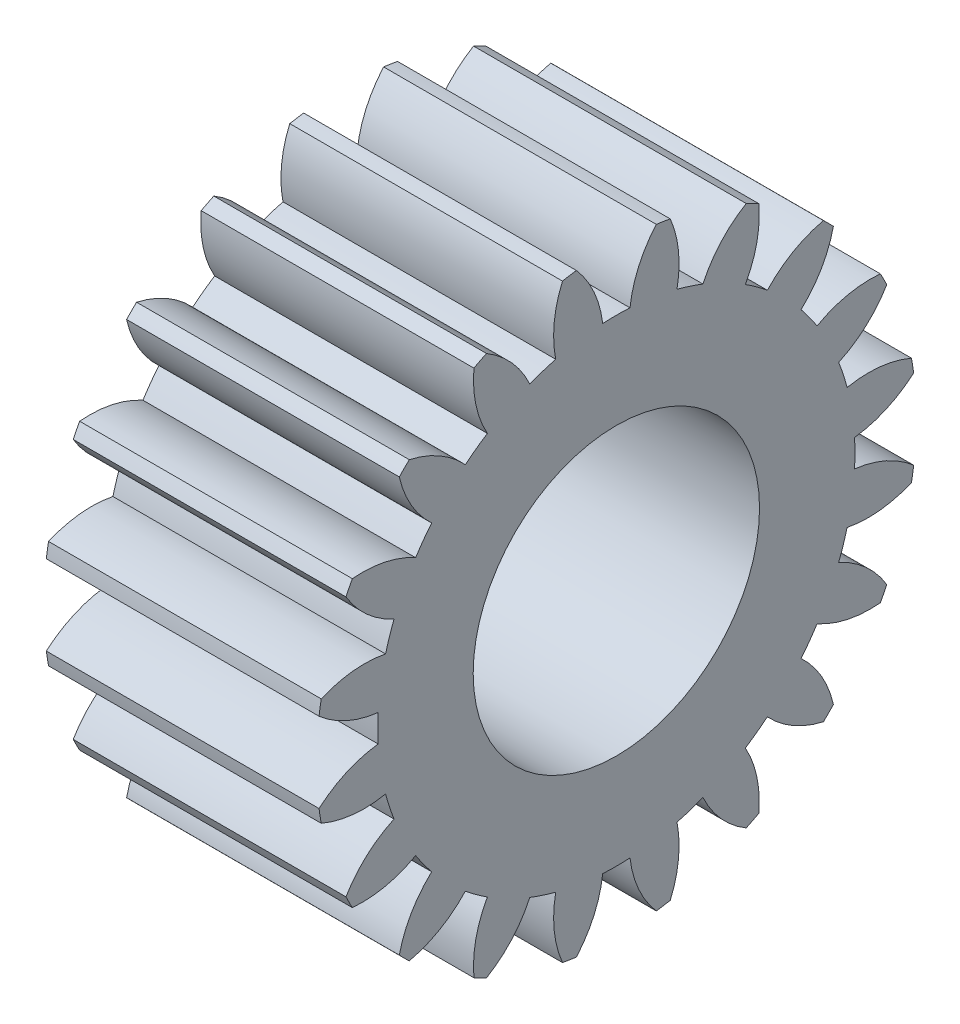
SolidWorks part; units mm, degrees
ref_plane "Plane1" through (0, 0, 0) normal (0, 0, 1) x (1, 0, 0)
ref_plane "Plane2" through (0, 0, 0) normal (0, 1, 0) x (1, 0, 0)
ref_plane "Plane3" through (0, 0, 0) normal (1, 0, 0) x (0, 0, -1)
sketch "HoldingSke" plane through (0, 0, 0) normal (0, 1, 0) x (1, 0, 0)
  line L0 (0, 0) -> (0.9397, -0.342)
  line L1 (-15, 0) -> (100, 0) construction
  line L2 (0, 0) -> (-2.1039, 2.3779)
  line L3 (0, 0) -> (-11.863, 4.5341)
  line L4 (0, 0) -> (8.1152, 2.9537)
  line L5 (0, 0) -> (-46.8476, -17.4728)
  line L6 (0, 0) -> (-8.2896, -5.593)
  line L7 (-2.1039, 2.3779) -> (8.6586, 51.2059)
  line L8 (-76.2, 54.61) -> (-76.1, 54.61)
  line L9 (-71.009, 38.7566) -> (-53.1078, 45.2721)
  line L10 (-76.2, 71.12) -> (104.1128, 71.12)
  line L11 (0, 0) -> (-10, 0)
  line L12 (-76.2, 101.6) -> (-76.162, 101.6)
  line L13 (24.9733, 27.94) -> (52.9518, 28.4284)
  line L14 (24.9733, 27.94) -> (24.9743, 27.94)
  line L15 (24.9733, 27.94) -> (100.4006, 29.5858)
  line L16 (-63.627, -1) -> (-12.827, -1)
  circle A0 centre (0, 0) radius 0.4
  circle A1 centre (0, 0) radius 8.749
  circle A2 centre (0, 0) radius 37.5
  circle A3 centre (0, 0) radius 0.4
  dimension "MHD" = 17.498
  dimension "Hub_dia" = 75
  dimension "Bore" = 0.8
  dimension "MBD" = 0.8
  dimension "Num_teeth" = 20
  dimension "Pitch" = 1
  dimension "Overall_len" = 50
  dimension "Show_teeth" = 20
  dimension "Thickness" = 10
  dimension "OAL" = 50.0001
  dimension "T_dim" = 0.1
  dimension "Ap" = 20
  dimension "H" = 19.05
  dimension "Pitch_radius" = 180.3128
  dimension "Width" = 10
  dimension "Backlash" = 0.038
  dimension "Addendum_fac" = 1
  dimension "Dedendum_fac" = 1.25
  dimension "Clearance_fac" = 0.25
  dimension "Dedendum_add" = 0.001
  dimension "Module" = 1
sketch "BasProSke" plane through (0, 0, 0) normal (0, 1, 0) x (1, 0, 0)
  line L0 (-10, 0) -> (60, 0) construction
  line L1 (0, 0) -> (0, 11)
  line L2 (0, 0) -> (10, 0)
  line L3 (10, 0) -> (10, 11)
  line L4 (10, 11) -> (0, 11)
  dimension "Thickness" = 10
  dimension "Diameter" = 22
revolve "Base-Revolve" add sketch "BasProSke" angle 360 about L0
sketch "TooCutSke" plane through (0, 0, 0) normal (1, 0, 0) x (0, 0, -1)
  line L1 (0, 0) -> (0, 107) construction
  line L2 (0, 0) -> (-0.8511, 9.9637) construction
  line L3 (0, 0) -> (-3.1206, 19.7028) construction
  line L4 (-0.8511, 9.9637) -> (-1.5603, 9.8514) construction
  arc A0 (0.4999, 8.7347) -> (-0.4999, 8.7347) centre (0, 0) ccw
  arc A1 (1.4852, 10.9249) -> (-1.4852, 10.9249) centre (0, 0) ccw
  circle A2 centre (0, 0) radius 10 construction
  circle A3 centre (0, 0) radius 9.3969 construction
  arc A4 (-0.4999, 8.7347) -> (-1.4852, 10.9249) centre (-4.4722, 8.2645) ccw
  arc A5 (1.4852, 10.9249) -> (0.4999, 8.7347) centre (4.4722, 8.2645) ccw
  dimension "Root_dia" = 17.498
  dimension "Overcut_dia" = 22.0508
  dimension "Pitch_dia" = 20
  dimension "Base_dia" = 18.7939
  dimension "Flank_rad" = 4
  dimension "Half_ang" = 9
  dimension "Half_CT" = 0.7181
extrude "ToothCut" cut sketch "TooCutSke" along normal through all
fillet "Breaks" [suppressed] radius 0.02 tangent propagation no
fillet "RootFillets" [suppressed] radius 0.251
pattern_circular "TeethCuts" count 20 every 18 about axis through (-10, 0, 0) along (1, 0, 0) of "ToothCut", "RootFillets", "Breaks"
sketch "HubNeaOneSke" plane through (0, 0, 0) normal (-1, 0, 0) x (0, 0, 1)
  circle A0 centre (0, 0) radius 8.749
  dimension "Diameter" = 17.498
extrude "HubNearOne" [suppressed] add sketch "HubNeaOneSke" along normal blind 40.0001
sketch "HubNeaBotSke" plane through (0, 0, 0) normal (-1, 0, 0) x (0, 0, 1)
  circle A0 centre (0, 0) radius 8.749
  dimension "Diameter" = 17.498
extrude "HubNearBoth" [suppressed] add sketch "HubNeaBotSke" along normal blind 20
ref_plane "FarPln" through (10, 0, 0) normal (1, 0, 0) x (0, 0, -1)
sketch "HubFarSke" plane through (10, 0, 0) normal (1, 0, 0) x (0, 0, -1)
  circle A0 centre (0, 0) radius 8.749
  dimension "Diameter" = 17.498
extrude "HubFar" [suppressed] add sketch "HubFarSke" along normal blind 20
sketch "BorSke" plane through (0, 0, 0) normal (1, 0, 0) x (0, 0, -1)
  circle A0 centre (0, 0) radius 0.4
  dimension "Diameter" = 0.8
extrude "Bore" cut sketch "BorSke" along normal mid plane 100.0001
sketch "KeySke" plane through (0, 0, 0) normal (1, 0, 0) x (0, 0, -1)
  line L0 (-0.05, 0) -> (-0.05, 0.5)
  line L1 (-0.05, 0.5) -> (0.05, 0.5)
  line L2 (0.05, 0.5) -> (0.05, 0)
  line L3 (0, 0) -> (0, 34) construction
  line L4 (-0.05, 0) -> (0.05, 0)
  dimension "Offset" = 0.5
  dimension "Width" = 0.1
extrude "Keyway" [suppressed] cut sketch "KeySke" along normal mid plane 100.0001
pattern_circular "Keyway2" [suppressed] count 2 every 90 about axis through (-10, 0, 0) along (1, 0, 0) reverse direction yes
hole_wizard "Taladro de margen para M101" positions "Croquis1" profile "Croquis2" hole size "M10" standard "ISO" end condition through all
sketch "Croquis1" plane through (10, 0, 0) normal (1, 0, 0) x (0, 0, -1)
  point P0 (0, 0)
sketch "Croquis2" plane through (10, 0, 0) normal (0, 1, 0) x (0, 0, -1)
  line L0 (0, 0) -> (0, 10)
  line L1 (0, 10) -> (5.25, 10)
  line L2 (5.25, 10) -> (5.25, 0)
  line L5 (5.25, 0) -> (0, 0)
  line L11 (0, -6.35) -> (0, 107.95) construction
  dimension "Diámetro de taladro hasta el siguiente" = 10.5
  dimension "Profundidad de taladro hasta el siguiente" = 10
equation "' \"Module@HoldingSke\" = 6.35"
equation "' \"Num_teeth@HoldingSke\" = 12"
equation "' \"Ap@HoldingSke\" =  20"
equation "' \"Ap@HoldingSke\" = 20"
equation "' \"Width@HoldingSke\" = 0.5 * 25.4"
equation "' \"Hub_dia@HoldingSke\"= 1 * 25.4"
equation "' \"Hub_dia@HoldingSke\" = 1 * 25.4"
equation "' \"Overall_len@HoldingSke\" = 1.0 * 25.4"
equation "' \"Bore@HoldingSke\" = 0.75 * 25.4"
equation "' \"T_dim@HoldingSke\" = 0.1 * 25.4"
equation "' \"Width@KeySke\" = 0.25 * 25.4"
equation "' \"Show_teeth@HoldingSke\" = 13"
equation "' \"Backlash@HoldingSke\" = 0.009 * 25.4"
equation "' \"Addendum_fac@HoldingSke\" = 1.0"
equation "' \"Dedendum_fac@HoldingSke\" = 1.25"
equation "' \"Dedendum_add@HoldingSke\" = 0.00005 * 25.4"
equation "' \"Clearance_fac@HoldingSke\" = 0.25"
equation "\"Pitch@HoldingSke\" = 1 / \"Module@HoldingSke\""
equation "\"Overcut_dia@TooCutSke\" = (\"Num_teeth@HoldingSke\" + 2 * \"Addendum_fac@HoldingSke\") / \"Pitch@HoldingSke\" + 0.002 * 25.4"
equation "\"Pitch_dia@TooCutSke\" = \"Num_teeth@HoldingSke\" / \"Pitch@HoldingSke\""
equation "\"Base_dia@TooCutSke\" = \"Num_teeth@HoldingSke\" / \"Pitch@HoldingSke\" * cos((\"Ap@HoldingSke\"  * 3.14159265 / 180))"
equation "\"Root_dia@TooCutSke\" = (\"Num_teeth@HoldingSke\" + 2) / \"Pitch@HoldingSke\" - 2 * (\"Addendum_fac@HoldingSke\" + \"Dedendum_fac@HoldingSke\") / \"Pitch@HoldingSke\" - \"Dedendum_add@HoldingSke\" * 2"
equation "\"Half_ang@TooCutSke\" = 180 / \"Num_teeth@HoldingSke\""
equation "\"Half_CT@TooCutSke\" = \"Num_teeth@HoldingSke\" / \"Pitch@HoldingSke\" * sin((3.14159265 / 2 / \"Num_teeth@HoldingSke\")) / 2 - 7 * \"Backlash@HoldingSke\" / 4"
equation "\"Flank_rad@TooCutSke\" = \"Num_teeth@HoldingSke\" / \"Pitch@HoldingSke\" / 5"
equation "\"Radius@RootFillets\" = \"Clearance_fac@HoldingSke\" / \"Pitch@HoldingSke\" + \"Dedendum_add@HoldingSke\""
equation "\"Break_rad@Breaks\" = 0.02 / \"Pitch@HoldingSke\""
equation "\"Thickness@HoldingSke\" = \"Width@HoldingSke\""
equation "\"OAL@HoldingSke\" = \"Thickness@HoldingSke\""
equation "\"MHD@HoldingSke\" = (\"Num_teeth@HoldingSke\" + 2) / \"Pitch@HoldingSke\" - 2 * (\"Addendum_fac@HoldingSke\" + \"Dedendum_fac@HoldingSke\")  / \"Pitch@HoldingSke\" - \"Dedendum_add@HoldingSke\" * 2"
equation "\"MBD@HoldingSke\" = (\"Num_teeth@HoldingSke\" + 2) / \"Pitch@HoldingSke\" - 2 * (\"Addendum_fac@HoldingSke\" + \"Dedendum_fac@HoldingSke\")  / \"Pitch@HoldingSke\" - \"Dedendum_add@HoldingSke\" * 2 - 0.002 * 25.4"
equation "\"MHD@HoldingSke\" = ((sgn( \"MHD@HoldingSke\" - \"Hub_dia@HoldingSke\" )-1)*( \"MHD@HoldingSke\" - \"Hub_dia@HoldingSke\" ))/-2+ \"Hub_dia@HoldingSke\""
equation "\"MBD@HoldingSke\" = ((sgn( \"MBD@HoldingSke\" - \"Bore@HoldingSke\" )-1)*( \"MBD@HoldingSke\" - \"Bore@HoldingSke\" ))/-2+ \"Bore@HoldingSke\""
equation "\"OAL@HoldingSke\" = ((sgn( \"OAL@HoldingSke\" - \"Overall_len@HoldingSke\" )+1)*( \"OAL@HoldingSke\" - \"Overall_len@HoldingSke\" ))/2 + \"Overall_len@HoldingSke\" + 0.000002 * 25.4"
equation "\"Num_teeth@TeethCuts\" = int( \"Show_teeth@HoldingSke\" ) + 1"
equation "\"Num_teeth@TeethCuts\" = ((sgn( \"Num_teeth@TeethCuts\" - \"Num_teeth@HoldingSke\" )-1)*( \"Num_teeth@TeethCuts\" - \"Num_teeth@HoldingSke\" ))/-2+ \"Num_teeth@HoldingSke\""
equation "\"Num_teeth@TeethCuts\" = ((sgn( \"Num_teeth@TeethCuts\" - 2.0)+1)*( \"Num_teeth@TeethCuts\" - 2.0))/2 +2.0"
equation "\"Angle@TeethCuts\" = 360.0 / \"Num_teeth@HoldingSke\""
equation "\"Diameter@BasProSke\" = (\"Num_teeth@HoldingSke\" + 2 * \"Addendum_fac@HoldingSke\") / \"Pitch@HoldingSke\""
equation "\"Thickness@BasProSke\"  = \"Thickness@HoldingSke\""
equation "' \"Fillet_rad@BasProSke\" =  \"Thickness@HoldingSke\" * 0.05"
equation "' \"Fillet_rad@BasProSke\" = \"Thickness@HoldingSke\" * 0.05"
equation "\"MHD@HoldingSke\" = ((sgn( \"MHD@HoldingSke\" - \"Root_dia@TooCutSke\" )-1)*( \"MHD@HoldingSke\" - \"Root_dia@TooCutSke\" ))/-2+ \"Root_dia@TooCutSke\""
equation "\"Diameter@HubNeaOneSke\" = \"MHD@HoldingSke\""
equation "\"Length@HubNearOne\" = \"OAL@HoldingSke\" - \"Thickness@BasProSke\""
equation "\"Diameter@HubNeaBotSke\" = \"MHD@HoldingSke\""
equation "\"Length@HubNearBoth\" = ( \"OAL@HoldingSke\" - \"Thickness@BasProSke\" ) / 2.0"
equation "\"Thickness@FarPln\" = \"Thickness@BasProSke\""
equation "\"Diameter@HubFarSke\" = \"MHD@HoldingSke\""
equation "\"Length@HubFar\" = ( \"OAL@HoldingSke\" - \"Thickness@BasProSke\" ) / 2.0"
equation "\"Diameter@BorSke\" = \"MBD@HoldingSke\""
equation "\"D1@Bore\" = \"OAL@HoldingSke\" * 2.0"
equation "\"D1@Keyway\" = \"OAL@HoldingSke\" * 2.0"
equation "\"Offset@KeySke\" = \"T_dim@HoldingSke\" + \"MBD@HoldingSke\" / 2.0"
